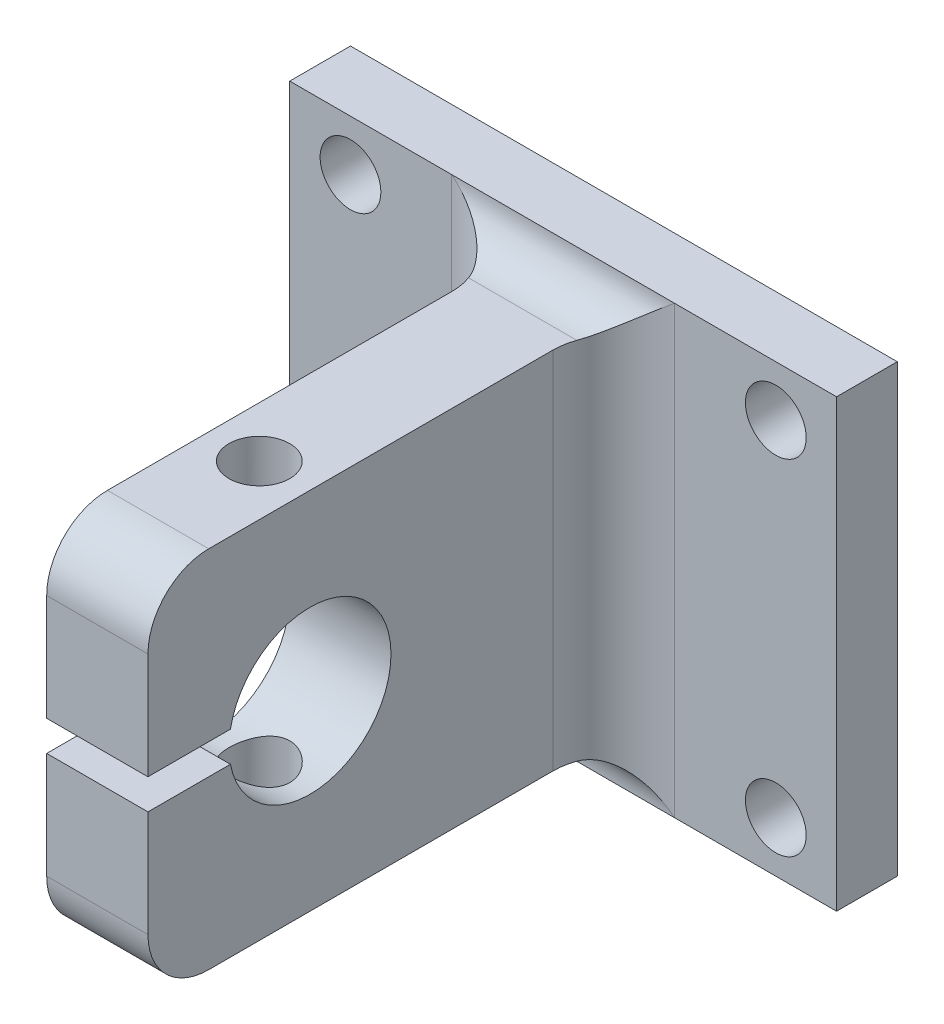
SolidWorks part; units mm, degrees
ref_plane "Front Plane" through (0, 0, 0) normal (0, 0, 1) x (1, 0, 0)
ref_plane "Top Plane" through (0, 0, 0) normal (0, 1, 0) x (1, 0, 0)
ref_plane "Right Plane" through (0, 0, 0) normal (1, 0, 0) x (0, 0, -1)
sketch "Sketch1" plane through (0, 0, 0) normal (0, 0, 1) x (1, 0, 0)
  line L1 (-13.5, -11) -> (13.5, -11)
  line L2 (-13.5, -11) -> (-13.5, 11)
  line L3 (-13.5, 11) -> (13.5, 11)
  line L4 (13.5, -11) -> (13.5, 11)
  line L5 (-13.5, -11) -> (13.5, 11) construction
  line L6 (-13.5, 11) -> (13.5, -11) construction
  line L7 (-10.5, -8.5) -> (-10.5, 8.5) construction
  line L8 (-10.5, 8.5) -> (10.5, 8.5) construction
  circle A5 centre (-10.5, -8.5) radius 1.5
  circle A6 centre (-10.5, 8.5) radius 1.5
  circle A7 centre (10.5, 8.5) radius 1.5
  circle A8 centre (10.5, -8.5) radius 1.5
  point P0 (0, 0)
  point P11 (-13.5, 0)
  point P12 (0, 11)
  point P13 (-10.5, 0)
  point P21 (0, 8.5)
  dimension "D5" = 3
  dimension "D1" = 27
  dimension "D2" = 22
  dimension "D6" = 17
  dimension "D7" = 21
extrude "Boss-Extrude1" add sketch "Sketch1" along normal blind 3
sketch "Sketch2" plane through (0, 0, 3) normal (0, 0, 1) x (1, 0, 0)
  line L1 (-2.5, 9) -> (2.5, 9)
  line L2 (-2.5, 9) -> (-2.5, -9)
  line L3 (-2.5, -9) -> (2.5, -9)
  line L4 (2.5, 9) -> (2.5, -9)
  line L5 (-13.5, -11) -> (13.5, -11) construction
  line L6 (2.5, 3.6093) -> (-2.5, 3.6093) construction
  line L7 (-13.5, 11) -> (-13.5, -11) construction
  point P4 (-13.5, 0)
  point P10 (0, -11)
  point P11 (0, 3.6093)
  point P16 (-2.5, 0)
  dimension "D1" = 5
  dimension "D2" = 18
extrude "Boss-Extrude2" add sketch "Sketch2" along normal blind 23
sketch "Sketch3" plane through (2.5, 0, 0) normal (1, 0, 0) x (0, 0, -1)
  line L0 (-26, -9) -> (-26, 9) construction
  line L1 (-3, -9) -> (-3, 9) construction
  circle A0 centre (-18, 0) radius 4
  point P5 (-26, 0)
  dimension "D1" = 8
  dimension "D2" = 15
extrude "Cut-Extrude1" cut sketch "Sketch3" against normal through all both and the other way through all
sketch "Sketch4" plane through (2.5, 0, 0) normal (1, 0, 0) x (0, 0, -1)
  line L1 (-26.2486, -0.75) -> (-16.7336, -0.75)
  line L2 (-26.2486, -0.75) -> (-26.2486, 0.75)
  line L3 (-26.2486, 0.75) -> (-16.7336, 0.75)
  line L4 (-16.7336, -0.75) -> (-16.7336, 0.75)
  line L5 (-26, -9) -> (-26, 9) construction
  point P6 (-26, 0)
  point P7 (-26.2486, 0)
  dimension "D1" = 1.5
extrude "Cut-Extrude2" cut sketch "Sketch4" against normal through all both and the other way through all
sketch "Sketch5" plane through (0, 11, 0) normal (0, 1, 0) x (1, 0, 0)
  line L0 (2.5, -26) -> (-2.5, -26) construction
  line L2 (2.5, -3) -> (-2.5, -3) construction
  circle A0 centre (0, -18) radius 1.5
  point P5 (0, -26)
  dimension "D1" = 3
  dimension "D2" = 15
fillet "Fillet1" radius 3 2 edges at (-2.5, 0, 3) (2.5, 0, 3)
extrude "Cut-Extrude3" cut sketch "Sketch5" against normal through all both and the other way through all
fillet "Fillet2" radius 2 2 edges at (0, 9, 3) (0, -9, 3)
fillet "Fillet3" radius 3 2 edges at (0, -9, 26) (0, 9, 26)
